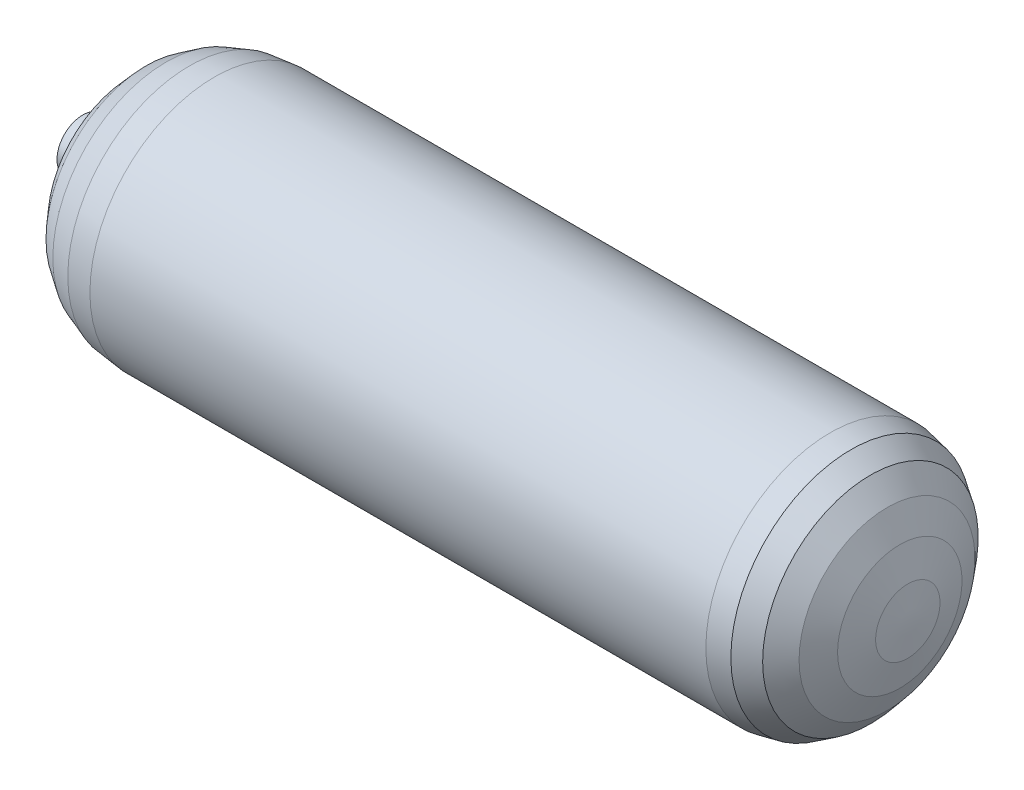
SolidWorks part; units mm, degrees
ref_plane "Front Plane" through (0, 0, 0) normal (0, 0, 1) x (1, 0, 0)
ref_plane "Top Plane" through (0, 0, 0) normal (0, 1, 0) x (1, 0, 0)
ref_plane "Right Plane" through (0, 0, 0) normal (1, 0, 0) x (0, 0, -1)
sketch "Bottle Sketch" plane through (0, 0, 0) normal (0, 0, 1) x (1, 0, 0)
  line L0 (-1000, 0) -> (1000, 0) construction
  line L1 (0, 0) -> (0, 16)
  line L2 (0, 16) -> (10, 16)
  line L3 (10, 16) -> (22, 26)
  line L4 (22, 26) -> (24.0445, 39.3292)
  line L5 (24.0445, 39.3292) -> (30.0385, 51.75)
  line L6 (30.0385, 51.75) -> (39.5736, 62.416)
  line L7 (39.5736, 62.416) -> (52, 70.6003)
  line L8 (52, 70.6003) -> (66.4709, 75.7452)
  line L9 (66.4709, 75.7452) -> (82, 77.5)
  line L10 (82, 77.5) -> (465.6, 77.5)
  line L11 (465.6, 77.5) -> (478.541, 74.8593)
  line L12 (478.541, 74.8593) -> (490.6, 67.117)
  line L13 (490.6, 67.117) -> (500.9553, 54.8008)
  line L14 (500.9553, 54.8008) -> (508.9013, 38.75)
  line L15 (508.9013, 38.75) -> (513.8963, 20.0585)
  line L16 (513.8963, 20.0585) -> (515.6, 0)
  line L17 (515.6, 0) -> (0, 0)
revolve "Bottle" add sketch "Bottle Sketch" angle 360 about L0
ref_axis "Engine Axis" through (541.38, 0, 0) along (-1, 0, 0)
ref_plane "Port Thread End" through (15, 0, 0) normal (1, 0, 0) x (0, 0, -1)
sketch "Port Bore Sketch" plane through (0, 0, 0) normal (0, 0, 1) x (1, 0, 0)
  line L0 (-1000, 0) -> (1000, 0) construction
  line L1 (-1, 0) -> (15, 0)
  line L2 (15, 0) -> (15, 10.1125)
  line L3 (15, 10.1125) -> (-1, 10.1125)
  line L4 (-1, 10.1125) -> (-1, 0)
revolve "Port Bore" cut sketch "Port Bore Sketch" angle 360 about L0
